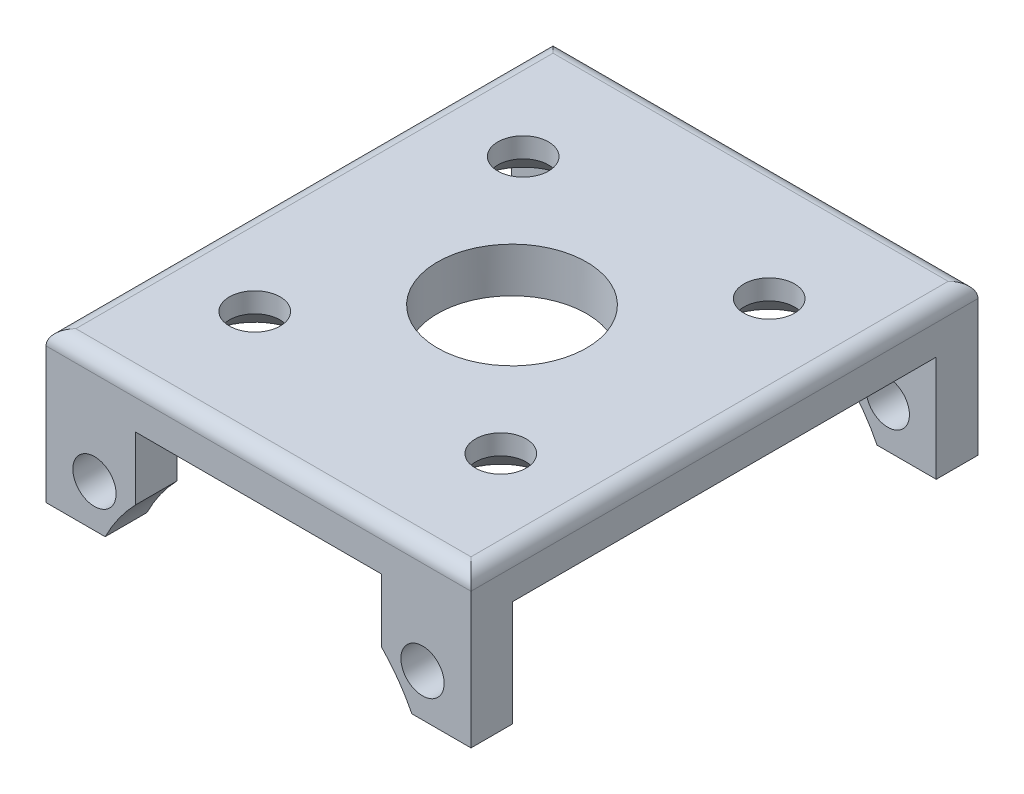
SolidWorks part; units mm, degrees
ref_plane "Front Plane" through (0, 0, 0) normal (0, 0, 1) x (1, 0, 0)
ref_plane "Top Plane" through (0, 0, 0) normal (0, 1, 0) x (1, 0, 0)
ref_plane "Right Plane" through (0, 0, 0) normal (1, 0, 0) x (0, 0, -1)
sketch "Sketch1" plane through (0, 0, 0) normal (0, 0, 1) x (1, 0, 0)
  line L0 (0, 0) -> (0, 5.0753) construction
  line L1 (-14.25, 11.25) -> (14.25, 11.25)
  line L2 (-14.25, 11.25) -> (-14.25, -35.25)
  line L3 (-14.25, -35.25) -> (14.25, -35.25)
  line L4 (14.25, 11.25) -> (14.25, -35.25)
  line L5 (-14.25, 11.25) -> (-7.75, 11.25)
  line L6 (-14.25, 11.25) -> (-14.25, 4.75)
  line L7 (-14.25, 4.75) -> (-7.75, 4.75)
  line L8 (-7.75, 11.25) -> (-7.75, 4.75)
  line L9 (0, 0) -> (3.7441, 0) construction
  line L10 (14.25, 4.75) -> (7.75, 4.75)
  line L11 (7.75, 11.25) -> (7.75, 4.75)
  line L12 (-14.25, -12) -> (23.601, -12) construction
  line L13 (7.75, -35.25) -> (7.75, -29.75)
  line L14 (14.25, -28.75) -> (8.75, -28.75)
  line L15 (-7.75, -35.25) -> (-7.75, -29.75)
  line L16 (-14.25, -28.75) -> (-8.75, -28.75)
  line L18 (14.25, 11.25) -> (-14.25, 11.25)
  line L19 (14.25, 11.25) -> (14.25, 15.25)
  line L20 (14.25, 15.25) -> (-14.25, 15.25)
  line L21 (-14.25, 11.25) -> (-14.25, 15.25)
  line L22 (-14.25, 4.75) -> (-16.25, 4.75)
  line L23 (-14.25, 4.75) -> (-14.25, 15.25)
  line L24 (-14.25, 15.25) -> (-16.25, 15.25)
  line L25 (-16.25, 4.75) -> (-16.25, 15.25)
  line L26 (14.25, 15.25) -> (16.25, 15.25)
  line L27 (14.25, 15.25) -> (14.25, 4.75)
  line L28 (14.25, 4.75) -> (16.25, 4.75)
  line L29 (16.25, 15.25) -> (16.25, 4.75)
  line L30 (-8.25, 11.25) -> (8.25, 11.25)
  line L31 (-8.25, 11.25) -> (-8.25, 4.75)
  line L32 (-8.25, 4.75) -> (8.25, 4.75)
  line L33 (8.25, 11.25) -> (8.25, 4.75)
  line L34 (-8.25, 11.25) -> (8.25, 11.25)
  line L35 (-8.25, 11.25) -> (-8.25, 12.25)
  line L36 (-8.25, 12.25) -> (8.25, 12.25)
  line L37 (8.25, 11.25) -> (8.25, 12.25)
  circle A1 centre (0, 0) radius 10.45
  circle A2 centre (-11, 8) radius 1.45
  circle A3 centre (11, 8) radius 1.45
  circle A4 centre (11, -32) radius 1.45
  circle A5 centre (-11, -32) radius 1.45
  arc A7 (-7.75, -29.75) -> (-8.75, -28.75) centre (-8.75, -29.75) ccw
  arc A8 (8.75, -28.75) -> (7.75, -29.75) centre (8.75, -29.75) ccw
  circle A9 centre (0, 0) radius 11.5
  point P0 (0, 0)
  point P35 (-7.75, -28.75)
  point P38 (7.75, -28.75)
  dimension "D1" = 28.5
  dimension "D2" = 46.5
  dimension "D3" = 23
  dimension "D4" = 11.25
  dimension "D5" = 2.9
  dimension "D6" = 3.25
  dimension "D7" = 3.25
  dimension "D10" = 3.25
  dimension "D12" = 1
  dimension "D16" = 20.9
  dimension "D17" = 0.5
  dimension "D11" = 3.25
  dimension "D13" = 4
  dimension "D14" = 2
  dimension "D15" = 2
  dimension "D18" = 0.5
  dimension "D19" = 1
  dimension "D8" = 2
  dimension "D9" = 2
extrude "Boss-Extrude7" add sketch "Sketch1" along normal blind 17 and the other way blind 17 contours L37 L18 L19 L20 L21 L1 L35 L36 | A9 L10 L4 L18 L33 A3 | A9 L31 L1 L2 L7 A2 region at (0, 13.5038, 0) region at (-11.25, 11.1615, 0) region at (14.1615, 8, 0)
sketch "Sketch34" plane through (-14.25, 0, 0) normal (-1, 0, 0) x (0, 0, 1)
  line L0 (-17, 4.75) -> (17, 4.75) construction
  line L1 (-14.2, 12.25) -> (14.2, 12.25)
  line L2 (-14.2, 12.25) -> (-14.2, 4.75)
  line L3 (-14.2, 4.75) -> (14.2, 4.75)
  line L4 (14.2, 12.25) -> (14.2, 4.75)
  line L5 (-17, 4.75) -> (-17, 15.25) construction
  line L6 (17, 4.75) -> (17, 15.25) construction
  line L7 (-17, 15.25) -> (17, 15.25) construction
  dimension "D1" = 2.8
  dimension "D2" = 2.8
  dimension "D3" = 3
extrude "Cut-Extrude11" cut sketch "Sketch34" against normal through all
sketch "Sketch35" plane through (0, 15.25, 0) normal (0, 1, 0) x (1, 0, 0)
  circle A0 centre (0, 0) radius 5
extrude "Cut-Extrude12" cut sketch "Sketch35" against normal through all
sketch "Sketch39" plane through (0, 12.25, 0) normal (0, -1, 0) x (1, 0, 0)
  line L0 (-14.25, 14.2) -> (-14.25, -14.2) construction
  line L1 (-8.25, 17) -> (8.25, 17) construction
  line L3 (0, 0) -> (0, 7.1623) construction
  line L4 (0, 0) -> (6.1391, 0) construction
  circle A0 centre (-8.25, 9) radius 1.5
  circle A1 centre (8.25, 9) radius 1.5
  circle A2 centre (-8.25, -9) radius 1.5
  circle A3 centre (8.25, -9) radius 1.5
  point P0 (-8.25, 9)
  point P9 (8.25, 9)
  point P12 (-8.25, -9)
  point P14 (8.25, -9)
  dimension "D1" = 6
  dimension "D2" = 8
hole_wizard "CSK for M3 Hex Socket Countersunk Cap Screw3" positions "Sketch39" profile "Sketch40" countersink size "M3" standard "ISO" end condition through all
sketch "Sketch40" plane through (-8.25, 12.25, 9) normal (1, 0, 0) x (0, 0, -1)
  line L0 (0, 0) -> (0, 3)
  line L1 (0, 3) -> (1.7, 3)
  line L2 (1.7, 3) -> (1.7, 1.66)
  line L3 (1.7, 1.66) -> (3.36, 0)
  line L5 (3.36, 0) -> (0, 0)
  line L6 (-1.7, 1.66) -> (-3.36, 0) construction
  line L11 (0, -6.35) -> (0, 107.95) construction
  dimension "Thru Hole Dia." = 3.4
  dimension "Thru Hole Depth" = 3
  dimension "Near C'Sink Dia." = 6.72
  dimension "Near C'Sink Angle" = 90
fillet "Fillet5" radius 1 4 edges at (14.25, 15.25, 0) (-14.25, 15.25, 0) (0, 15.25, -17) (0, 15.25, 17)
sketch "Sketch41" plane through (0, 0, 17) normal (0, 0, 1) x (1, 0, 0)
  line L0 (14.25, 4.75) -> (14.25, 14.25) construction
  line L1 (-14.25, 4.75) -> (14.25, 4.75)
  line L2 (-14.25, 4.75) -> (-14.25, 5.15)
  line L3 (-14.25, 5.15) -> (14.25, 5.15)
  line L4 (14.25, 4.75) -> (14.25, 5.15)
  dimension "D1" = 0.4
extrude "Cut-Extrude13" cut sketch "Sketch41" against normal through all
